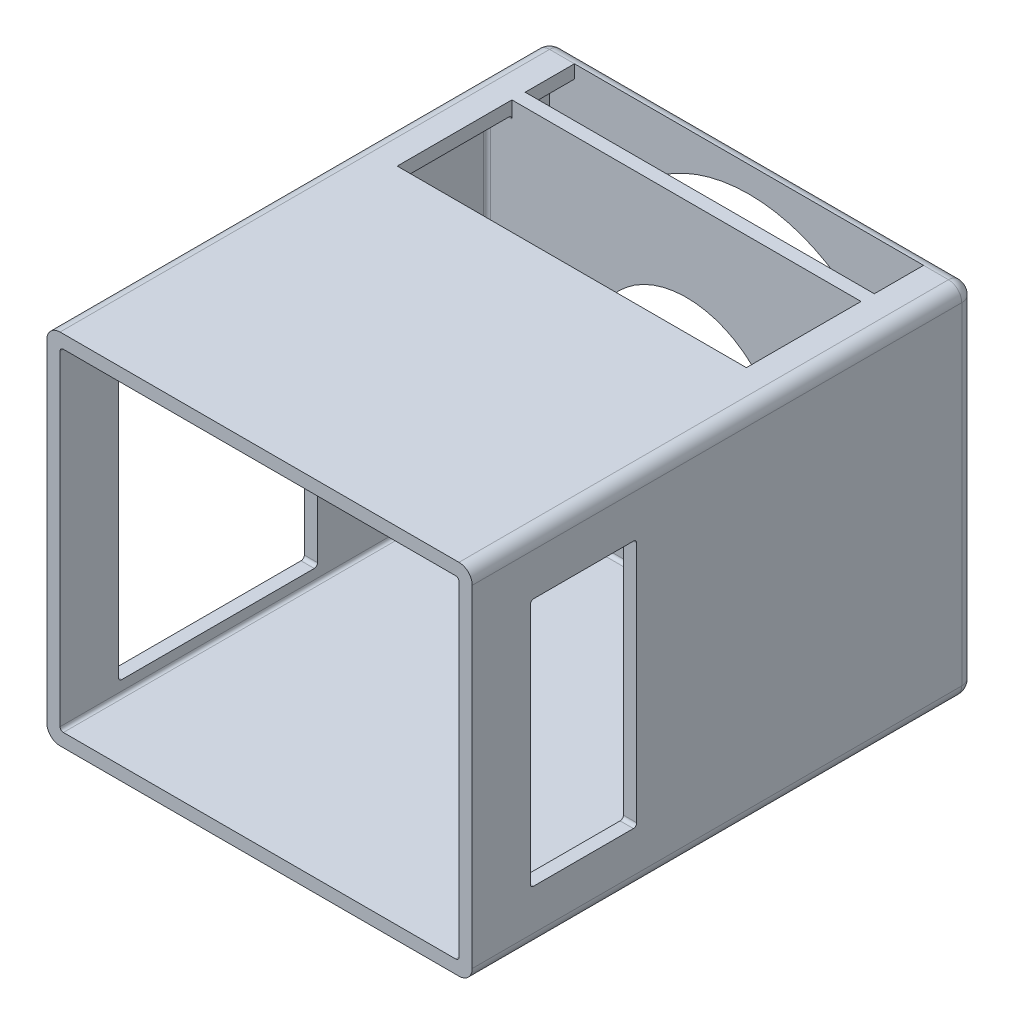
SolidWorks part; units mm, degrees
ref_plane "Front Plane" through (0, 0, 0) normal (0, 0, 1) x (1, 0, 0)
ref_plane "Top Plane" through (0, 0, 0) normal (0, 1, 0) x (1, 0, 0)
ref_plane "Right Plane" through (0, 0, 0) normal (1, 0, 0) x (0, 0, -1)
sketch "Sketch2" plane through (0, 0, 0) normal (0, 1, 0) x (1, 0, 0)
  line L0 (256.4, 0) -> (248.4, 0)
  line L1 (0, 0) -> (256.4, 0) construction
  line L2 (0, 0) -> (0, 268) construction
  line L3 (0, 268) -> (256.4, 268) construction
  line L4 (256.4, 0) -> (256.4, 268) construction
  line L5 (248.4, 0) -> (248.4, 260)
  line L6 (248.4, 260) -> (8, 260)
  line L7 (8, 260) -> (8, 0)
  line L8 (8, 0) -> (0, 0)
  line L9 (0, 0) -> (0, 268)
  line L10 (0, 268) -> (256.4, 268)
  line L11 (256.4, 268) -> (256.4, 0)
  dimension "D1" = 256.4
  dimension "D2" = 268
  dimension "D3" = 8
  dimension "D4" = 8
  dimension "D5" = 8
extrude "Boss-Extrude1" add sketch "Sketch2" along normal blind 216
sketch "Sketch3" plane through (0, 0, 0) normal (0, -1, 0) x (1, 0, 0)
  line L1 (248.4, -260) -> (8, -260)
  line L2 (248.4, -260) -> (248.4, 0)
  line L3 (248.4, 0) -> (8, 0)
  line L4 (8, -260) -> (8, 0)
extrude "Boss-Extrude2" add sketch "Sketch3" against normal blind 8
sketch "Sketch4" plane through (0, 0, -268) normal (0, 0, -1) x (-1, 0, 0)
  line L0 (0, 216) -> (0, 0) construction
  line L2 (-256.4, 0) -> (0, 0) construction
  circle A0 centre (-128.2, 108) radius 100
  dimension "D1" = 128.2
  dimension "D2" = 108
  dimension "D3" = 200
extrude "Cut-Extrude1" cut sketch "Sketch4" against normal blind 8 draft 42.885
ref_plane "Plane1" through (0, 0, -230.3) normal (0, 0, 1) x (1, 0, 0)
sketch "Sketch6" plane through (0, 0, -230.3) normal (0, 0, 1) x (1, 0, 0)
  line L1 (8, 216) -> (248.4, 216)
  line L2 (8, 216) -> (8, 8)
  line L3 (8, 8) -> (248.4, 8)
  line L4 (248.4, 216) -> (248.4, 8)
extrude "Boss-Extrude3" add sketch "Sketch6" along normal blind 8
sketch "Sketch7" plane through (0, 0, -230.3) normal (0, 0, -1) x (-1, 0, 0)
  circle A0 centre (-128.2, 108) radius 64.9391
  dimension "D1" = 129.8782
extrude "Cut-Extrude2" cut sketch "Sketch7" against normal blind 8 draft 42.885 contours A0
sketch "Sketch8" plane through (0, 0, 0) normal (-1, 0, 0) x (0, 0, 1)
  line L0 (0, 216) -> (0, 0) construction
  line L1 (-70.3, 208) -> (0, 208)
  line L2 (-70.3, 208) -> (-70.3, 8)
  line L3 (-70.3, 8) -> (0, 8)
  line L4 (0, 208) -> (0, 8)
  line L5 (-268, 216) -> (0, 216) construction
  line L6 (-268, 0) -> (0, 0) construction
  dimension "D1" = 70.3
  dimension "D2" = 8
  dimension "D3" = 8
extrude "Cut-Extrude3" cut sketch "Sketch8" against normal blind 8
ref_plane "Plane2" through (0, 0, 35) normal (0, 0, 1) x (1, 0, 0)
sketch "Sketch9" plane through (0, 0, 35) normal (0, 0, 1) x (1, 0, 0)
  line L1 (0, 216) -> (256.4, 216)
  line L2 (0, 216) -> (0, 0)
  line L3 (0, 0) -> (256.4, 0)
  line L4 (256.4, 216) -> (256.4, 0)
  line L5 (248.4, 8) -> (8, 8)
  line L6 (248.4, 8) -> (248.4, 208)
  line L7 (248.4, 208) -> (8, 208)
  line L8 (8, 8) -> (8, 208)
extrude "Boss-Extrude4" add sketch "Sketch9" against normal blind 35.2
sketch "Sketch11" plane through (0, 216, 0) normal (0, 1, 0) x (1, 0, 0)
  line L0 (0, 31.0856) -> (0, 174.2731) construction
  line L1 (0, 268) -> (0, -35) construction
sketch "Sketch12" plane through (0, 216, 0) normal (0, 1, 0) x (1, 0, 0)
  line L0 (8, 0.2) -> (8, 222.3) construction
  line L1 (8, 153.2035) -> (248.4, 153.2035)
  line L2 (8, 153.2035) -> (8, 0.2)
  line L3 (8, 0.2) -> (248.4, 0.2)
  line L4 (248.4, 153.2035) -> (248.4, 0.2)
  line L5 (248.4, 222.3) -> (248.4, 0.2) construction
extrude "Boss-Extrude6" add sketch "Sketch12" against normal blind 8
sketch "Sketch13" plane through (256.4, 0, 0) normal (1, 0, 0) x (0, 0, -1)
  line L0 (-35, 216) -> (268, 216) construction
  line L1 (0, 182.5) -> (64.1104, 182.5)
  line L2 (0, 182.5) -> (0, 32.5)
  line L3 (0, 32.5) -> (64.1104, 32.5)
  line L4 (64.1104, 182.5) -> (64.1104, 32.5)
  dimension "D1" = 150
  dimension "D2" = 33.5
extrude "Cut-Extrude6" cut sketch "Sketch13" against normal blind 8
sketch "Sketch15" plane through (0, 0, 0) normal (-1, 0, 0) x (0, 0, 1)
  line L0 (-70.3, 208) -> (-70.3, 8) construction
  line L1 (-120.2, 16) -> (-70.3, 16)
  line L2 (-120.2, 16) -> (-120.2, 200)
  line L3 (-120.2, 200) -> (-70.3, 200)
  line L4 (-70.3, 16) -> (-70.3, 200)
  line L5 (-0.2, 208) -> (-0.2, 8) construction
  line L6 (-268, 0) -> (35, 0) construction
  line L7 (-31.0856, 216) -> (-174.2731, 216) construction
  dimension "D1" = 120
  dimension "D2" = 16
  dimension "D3" = 16
extrude "Cut-Extrude8" cut sketch "Sketch15" against normal blind 8
sketch "Sketch16" plane through (0, 0, 0) normal (-1, 0, 0) x (0, 0, 1)
  line L0 (-70.3, 8) -> (-0.2, 8) construction
  line L1 (-70.3, 16) -> (-0.1, 16)
  line L2 (-70.3, 16) -> (-70.3, 8)
  line L3 (-70.3, 8) -> (-0.1, 8)
  line L4 (-0.1, 16) -> (-0.1, 8)
  line L5 (-0.2, 208) -> (-0.2, 8) construction
  line L6 (-70.3, 208) -> (-0.2, 208)
  line L7 (-70.3, 208) -> (-70.3, 200)
  line L8 (-70.3, 200) -> (-0.2, 200)
  line L9 (-0.2, 208) -> (-0.2, 200)
  dimension "D1" = 8
  dimension "D2" = 70.2
extrude "Boss-Extrude7" add sketch "Sketch16" against normal blind 8
sketch "Sketch17" plane through (256.4, 0, 0) normal (1, 0, 0) x (0, 0, -1)
  line L0 (64.1104, 107.5) -> (268, 108) construction
  line L1 (64.1104, 32.5) -> (64.1104, 182.5) construction
  line L2 (268, 216) -> (268, 0) construction
  line L4 (180.5552, 92.75) -> (151.5552, 92.75)
  line L5 (180.5552, 92.75) -> (180.5552, 122.75)
  line L6 (180.5552, 122.75) -> (151.5552, 122.75)
  line L7 (151.5552, 92.75) -> (151.5552, 122.75)
  line L8 (180.5552, 92.75) -> (151.5552, 122.75) construction
  line L9 (180.5552, 122.75) -> (151.5552, 92.75) construction
  point P6 (166.0552, 107.75)
  dimension "D1" = 29
  dimension "D2" = 30
sketch "Sketch19" plane through (0, 216, 0) normal (0, 1, 0) x (1, 0, 0)
  line L0 (248.4, 153.2035) -> (8, 153.2035) construction
  line L1 (8, 260) -> (23, 260)
  line L2 (8, 260) -> (8, 153.2035)
  line L3 (8, 153.2035) -> (23, 153.2035)
  line L4 (23, 260) -> (23, 153.2035)
  line L6 (248.4, 260) -> (233.4, 260)
  line L7 (248.4, 260) -> (248.4, 153.2035)
  line L8 (248.4, 153.2035) -> (233.4, 153.2035)
  line L9 (233.4, 260) -> (233.4, 153.2035)
  dimension "D1" = 15
  dimension "D2" = 15
extrude "Boss-Extrude8" add sketch "Sketch19" against normal blind 8
fillet "Fillet2" radius 8 8 edges at (0, 108, -268) (128.2, 0, -268) (128.2, 216, -268) (256.4, 108, -268) (256.4, 0, -116.5) (256.4, 216, -116.5) (0, 216, -116.5) (0, 0, -116.5)
fillet "Fillet3" radius 2 4 edges at (248.4, 8, -93.65) (8, 8, -93.65) (248.4, 208, -93.65) (8, 208, -93.65)
fillet "Fillet4" radius 2 9 edges at (16.5, 208, -222.3) (8.5858, 207.4142, -222.3) (8.5858, 8.5858, -222.3) (247.8142, 8.5858, -222.3) (239.9, 208, -222.3) (247.8142, 207.4142, -222.3) (8, 108, -222.3) (128.2, 8, -222.3) (248.4, 108, -222.3)
fillet "Fillet5" radius 2 8 edges at (252.4, 32.5, 0) (252.4, 32.5, -64.1104) (252.4, 182.5, 0) (252.4, 182.5, -64.1104) (4, 200, -120.2) (4, 16, -120.2) (4, 16, -0.2) (4, 200, -0.2)
sketch "Sketch20" plane through (0, 0, 0) normal (-1, 0, 0) x (0, 0, 1)
  line L1 (-180.5552, 92.75) -> (-151.5552, 92.75)
  line L2 (-180.5552, 92.75) -> (-180.5552, 122.75)
  line L3 (-180.5552, 122.75) -> (-151.5552, 122.75)
  line L4 (-151.5552, 92.75) -> (-151.5552, 122.75)
  line L5 (-180.5552, 92.75) -> (-151.5552, 122.75) construction
  line L6 (-180.5552, 122.75) -> (-151.5552, 92.75) construction
  point P0 (-166.0552, 107.75)
extrude "Cut-Extrude9" cut sketch "Sketch20" against normal blind 10
fillet "Fillet6" radius 2 4 edges at (4, 122.75, -151.5552) (4, 122.75, -180.5552) (4, 92.75, -180.5552) (4, 92.75, -151.5552)
sketch "Sketch22" plane through (0, 0, 0) normal (-1, 0, 0) x (0, 0, 1)
  line L0 (-260, 208) -> (-260, 8) construction
  line L1 (-260, 8) -> (35, 8) construction
  line L2 (35, 208) -> (35, 8) construction
  line L3 (35, 8) -> (35, 208) construction
  line L4 (35, 208) -> (-260, 208) construction
  line L5 (-31.0856, 216) -> (-174.2731, 216) construction
  line L6 (-268, 8) -> (-268, 208) construction
  line L7 (35, 0) -> (-260, 0) construction
  line L9 (-120.2, 200) -> (-120.2, 16) construction
  line L10 (-120.2, 16) -> (-0.2, 16) construction
  line L11 (-268, 167.179) -> (35, 167.179) construction
  line L12 (-0.2, 94.3764) -> (35, 94.3764) construction
  line L13 (-0.2, 198) -> (-0.2, 18) construction
  line L14 (-100.0798, 208) -> (-100.0798, 200) construction
  line L15 (-2.2, 200) -> (-118.2, 200) construction
  point P25 (-60.2, 16)
  dimension "D1" = 8
  dimension "D2" = 8
  dimension "D3" = 8
